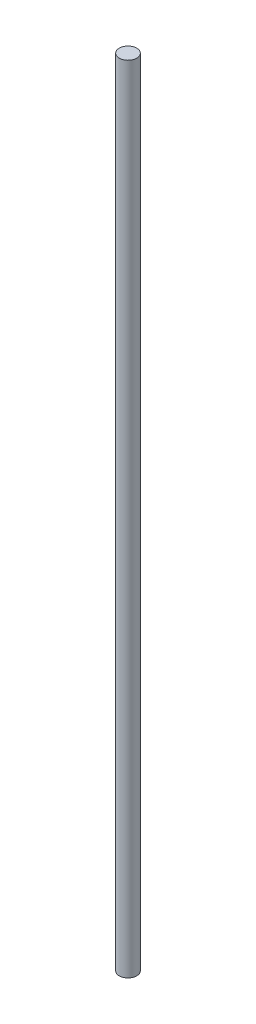
SolidWorks part; units mm, degrees
ref_plane "Front Plane" through (0, 0, 0) normal (0, 0, 1) x (1, 0, 0)
ref_plane "Top Plane" through (0, 0, 0) normal (0, 1, 0) x (1, 0, 0)
ref_plane "Right Plane" through (0, 0, 0) normal (1, 0, 0) x (0, 0, -1)
sketch "Sketch1" plane through (0, 0, 0) normal (0, 1, 0) x (1, 0, 0)
  circle A0 centre (0, 0) radius 3
  dimension "D1" = 6
extrude "Boss-Extrude1" add sketch "Sketch1" along normal blind 273
